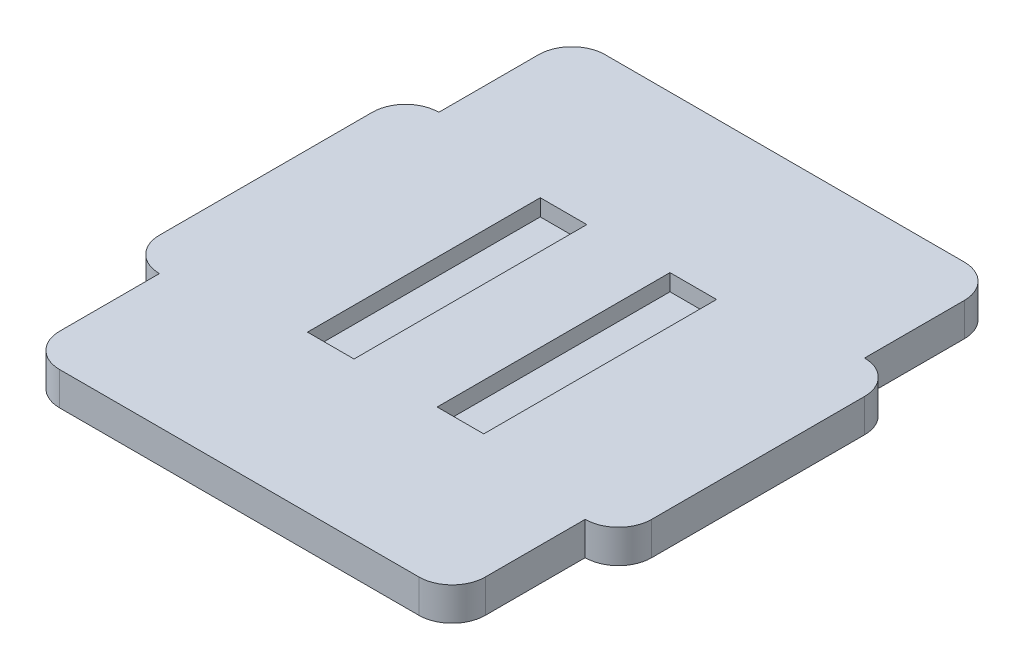
SolidWorks part; units mm, degrees
ref_plane "Front Plane" through (0, 0, 0) normal (0, 0, 1) x (1, 0, 0)
ref_plane "Top Plane" through (0, 0, 0) normal (0, 1, 0) x (1, 0, 0)
ref_plane "Right Plane" through (0, 0, 0) normal (1, 0, 0) x (0, 0, -1)
sketch "Sketch2" plane through (0, 0, 0) normal (0, 1, 0) x (1, 0, 0)
  line L0 (28, 21) -> (35, 21) construction
  line L1 (0, 0) -> (28, 0)
  line L2 (0, 0) -> (0, 42)
  line L3 (0, 42) -> (28, 42)
  line L4 (28, 0) -> (28, 42)
  line L5 (28, 42) -> (35, 42)
  line L6 (28, 42) -> (28, 0)
  line L7 (28, 0) -> (35, 0)
  line L8 (35, 42) -> (35, 0)
  line L9 (28, 38.5) -> (35, 38.5)
  line L10 (31.5, 38.5) -> (31.5, 3.5) construction
  line L11 (28, 3.5) -> (35, 3.5)
  line L12 (26, 0) -> (26, 42)
  line L13 (28, 42) -> (35, 42)
  line L14 (35, 42) -> (37, 42)
  line L15 (35, 42) -> (35, 0)
  line L16 (35, 0) -> (37, 0)
  line L17 (37, 42) -> (37, 0)
  line L18 (37, 42) -> (46, 42)
  line L19 (37, 42) -> (46, 42)
  line L22 (51, 37) -> (51, 5)
  line L23 (2, 42) -> (2, 0)
  line L24 (0, 38.5) -> (-7, 38.5)
  line L25 (0, 3.5) -> (-7, 3.5)
  line L26 (-7, 38.5) -> (-7, 3.5)
  line L27 (0, 42) -> (-7, 42)
  line L28 (-7, 42) -> (-7, 38.5)
  line L29 (0, 0) -> (-7, 0)
  line L30 (-7, 0) -> (-7, 3.5)
  line L31 (-7, 42) -> (-9, 42)
  line L32 (-9, 42) -> (-9, 0)
  line L33 (-9, 0) -> (-7, 0)
  line L34 (-9, 0) -> (-18, 0)
  line L35 (-23, 5) -> (-23, 37)
  line L36 (-18, 42) -> (-9, 42)
  line L37 (37, 0) -> (46, 0)
  line L39 (-18, 0) -> (46, 0)
  line L40 (-18, 0) -> (-18, -15)
  line L41 (-13, -20) -> (41, -20)
  line L42 (46, 0) -> (46, -15)
  line L43 (-18, 42) -> (46, 42)
  line L44 (-18, 42) -> (-18, 57)
  line L45 (-13, 62) -> (41, 62)
  line L46 (46, 42) -> (46, 57)
  arc A0 (51, 37) -> (46, 42) centre (46, 37) ccw
  arc A2 (-18, 0) -> (-23, 5) centre (-18, 5) cw
  arc A3 (-23, 37) -> (-18, 42) centre (-18, 37) cw
  arc A4 (46, 0) -> (51, 5) centre (46, 5) ccw
  arc A5 (-13, -20) -> (-18, -15) centre (-13, -15) cw
  arc A6 (41, -20) -> (46, -15) centre (41, -15) ccw
  arc A7 (46, 57) -> (41, 62) centre (41, 57) ccw
  arc A8 (-13, 62) -> (-18, 57) centre (-13, 57) ccw
  point P56 (46, -20)
  point P61 (-18, 62)
  dimension "D9" = 5
  dimension "D10" = 5
  dimension "D18" = 5
  dimension "D19" = 5
  dimension "D1" = 28
  dimension "D2" = 42
  dimension "D3" = 7
  dimension "D4" = 3.5
  dimension "D5" = 3.5
  dimension "D6" = 2
  dimension "D7" = 2
  dimension "D8" = 3.5
  dimension "D11" = 14
  dimension "D12" = 20
  dimension "D13" = 20
  dimension "D14" = 2
  dimension "D15" = 7
  dimension "D16" = 2
  dimension "D17" = 14
  dimension "D20" = 82
  dimension "D21" = 64
extrude "Boss-Extrude1" add sketch "Sketch2" along normal blind 5 contours L3 L23 L1 L12 | L12 L1 L4 L6 L3 | L11 L4 L7 L8 | L22 A0 L18 L17 | L17 L14 L8 L16 | L6 L9 L8 L5 | A3 L35 A2 L34 L32 L36 | L30 L29 L2 L25 | L32 L33 L30 L26 L28 L31 | L23 L3 L2 L1 | L27 L28 L24 L2 | L41 A6 L42 L37 L16 L7 L1 L29 L33 L34 L40 A5 | L45 A8 L44 L36 L31 L27 L3 L5 L14 L18 L46 A7 region at (1, 0, -21) region at (-3.5, 0, -1.75) region at (14, 0, 9.9249) region at (14, 0, -21) region at (-8, 0, -21) region at (27, 0, -21) region at (14, 0, -51.9249) region at (-3.5, 0, -40.25) region at (-15.8906, 0, -21) region at (31.5, 0, -1.75) region at (36, 0, -21) region at (31.5, 0, -40.25) region at (43.8906, 0, -21)
extrude "Boss-Extrude2" add sketch "Sketch2<3>" along normal blind 5 contours L24 L26 L25 L2 | L6 L11 L8 L9 region at (-3.5, 0, -21) region at (31.5, 0, -21)
sketch "Sketch2<3>" plane through (0, 0, 0) normal (0, 1, 0) x (1, 0, 0) same geometry as "Sketch2"
sketch "Sketch3" plane through (0, 5, 0) normal (0, 1, 0) x (1, 0, 0)
  line L16 (14, -20) -> (14, 62) construction
  line L17 (27.25, 38.5) -> (20.25, 38.5)
  line L18 (27.25, 38.5) -> (27.25, 3.5)
  line L19 (27.25, 3.5) -> (20.25, 3.5)
  line L20 (20.25, 38.5) -> (20.25, 3.5)
  line L21 (0.75, 38.5) -> (7.75, 38.5)
  line L22 (0.75, 38.5) -> (0.75, 3.5)
  line L23 (0.75, 3.5) -> (7.75, 3.5)
  line L24 (7.75, 38.5) -> (7.75, 3.5)
  line L25 (-13, -20) -> (41, -20) construction
  line L26 (-13, 62) -> (41, 62) construction
  point P0 (0.75, 21)
  point P1 (14, 21)
  dimension "D1" = 35
  dimension "D2" = 7
  dimension "D3" = 7
  dimension "D4" = 6.25
  dimension "D5" = 6.25
  dimension "D6" = 35
extrude "Cut-Extrude1" cut sketch "Sketch3" against normal blind 2.5
